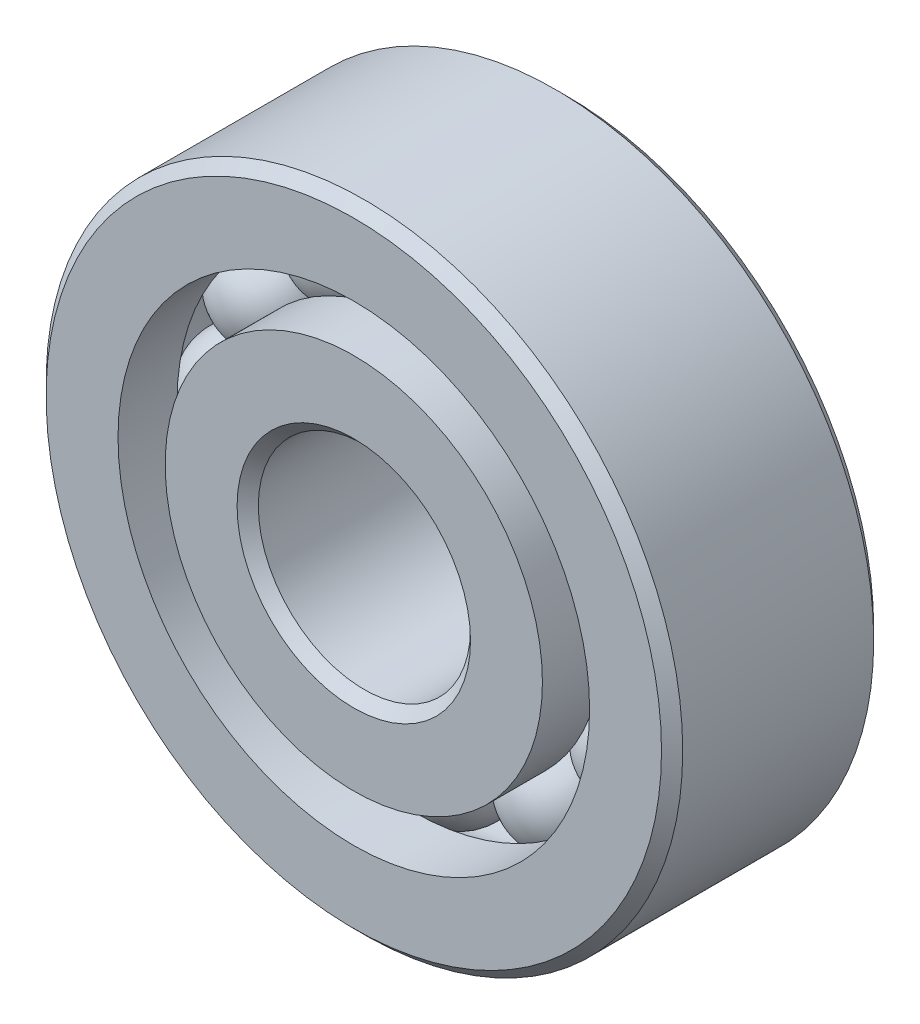
SolidWorks part; units mm, degrees
material "AISI 304"
ref_plane "Front Plane" through (0, 0, 0) normal (0, 0, 1) x (1, 0, 0)
ref_plane "Top Plane" through (0, 0, 0) normal (0, 1, 0) x (1, 0, 0)
ref_plane "Right Plane" through (0, 0, 0) normal (1, 0, 0) x (0, 0, -1)
sketch "Sketch1" plane through (0, 0, 0) normal (1, 0, 0) x (0, 0, -1)
  line L0 (-0.5, 0) -> (0.5, 0) construction
  line L1 (0, 1.5) -> (0, -1.5) construction
  line L2 (0.45, 1.5) -> (-0.45, 1.5)
  line L3 (-0.45, 1.5) -> (-0.5, 1.45)
  line L4 (-0.5, 1.45) -> (-0.5, 1.1111)
  line L5 (-0.5, 1.1111) -> (-0.2222, 1.1111)
  line L6 (0.5, 1.1111) -> (0.2222, 1.1111)
  line L7 (0.5, 1.45) -> (0.5, 1.1111)
  line L8 (0.45, 1.5) -> (0.5, 1.45)
  line L9 (0, 1.5) -> (0, 1) construction
  line L10 (0, 1) -> (0, 0.5) construction
  arc A0 (-0.2222, 1.1111) -> (0.2222, 1.1111) centre (0, 1) cw
  arc A1 (-0.2222, 1.1111) -> (0.2222, 1.1111) centre (0, 1) ccw construction
  point P14 (0, 0.5)
  point P15 (0, -0.5)
  dimension "Width" = 1
  dimension "OD" = 3
  dimension "D1" = 45
  dimension "D2" = 0.05
  dimension "D3" = 0.4444
  dimension "Shaft Dia" = 1
  dimension "D4" = 0.1111
revolve "Revolve1" add sketch "Sketch1" angle 360 about L0
sketch "Sketch2" plane through (0, 0, 0) normal (1, 0, 0) x (0, 0, -1)
  line L0 (-0.5, 0.8889) -> (-0.2222, 0.8889)
  line L1 (-0.5, 1.45) -> (-0.5, -1.45) construction
  line L2 (-0.5, 0.8889) -> (-0.5, 0.55)
  line L3 (-0.5, 0.55) -> (-0.45, 0.5)
  line L4 (-0.45, 0.5) -> (0.45, 0.5)
  line L5 (0, 1.5) -> (0, -1.5) construction
  line L6 (0, 0.5) -> (0, 0.7515) construction
  line L7 (0, 0.7515) -> (0, 0.5) construction
  line L8 (-0.5, 0.8889) -> (-0.5, 0.2111) construction
  line L10 (0.5, 0.8889) -> (0.2222, 0.8889)
  line L11 (0.5, 0.8889) -> (0.5, 0.55)
  line L12 (0.5, 0.55) -> (0.45, 0.5)
  arc A0 (-0.2222, 0.8889) -> (0.2222, 0.8889) centre (0, 1) ccw
  arc A1 (0.2222, 1.1111) -> (-0.2222, 1.1111) centre (0, 1) ccw construction
  circle A2 centre (0, 1) radius 0.2485 construction
  dimension "D1" = 0.05
  dimension "D2" = 45
revolve "Revolve2" add sketch "Sketch2" angle 360 about L0
sketch "Sketch3" plane through (0, 0, 0) normal (1, 0, 0) x (0, 0, -1)
  line L0 (-0.2485, 1) -> (0.2485, 1)
  line L1 (0, 1) -> (0, 0) construction
  circle A1 centre (0, 1) radius 0.2485 construction
  arc A2 (-0.2485, 1) -> (0.2485, 1) centre (0, 1) cw
  arc A3 (0.2222, 1.1111) -> (-0.2222, 1.1111) centre (0, 1) ccw construction
  dimension "D1" = 0.4969
revolve "Revolve3" add sketch "Sketch3" angle 360 about L0
ref_axis "Axis1" through (0, 0, -0.5) along (0, 0, 1)
pattern_circular "CirPattern1" count 12 every 30 about axis through (0, 0, -0.5) along (0, 0, 1) of bodies 104
sketch "Sketch6" plane through (0, 0, 0) normal (0, 1, 0) x (1, 0, 0)
  point P0 (1.5, -0.5)
  point P1 (1.5, 0.5)
ref_axis "Center Axis 1" through (0, 0, -0.7118) along (0, 0, 1)
ref_plane "Contact Plane 1" through (0, 0, 0.5) normal (0, 0, 1) x (1, 0, 0)
ref_plane "Contact Plane 2" through (0, 0, -0.5) normal (0, 0, -1) x (-1, 0, 0)
equation "\"D2@Sketch1\" = \"Width@Sketch1\"*.05"
equation "\"D3@Sketch1\" = \"Width@Sketch1\"/2.25"
equation "\"D4@Sketch1\" = \"D3@Sketch1\"/4"
equation "\"Balls@CirPattern1\"=\"D2@Sketch3\"*2*pi/\"D1@Sketch3\"-1"
equation "\"D2@CirPattern1\" = 360/\"Balls@CirPattern1\""
equation "\"D1@Sketch2\"=\"D2@Sketch1\""
equation "\"D1@Sketch6\"=\"Width@Sketch1\""
